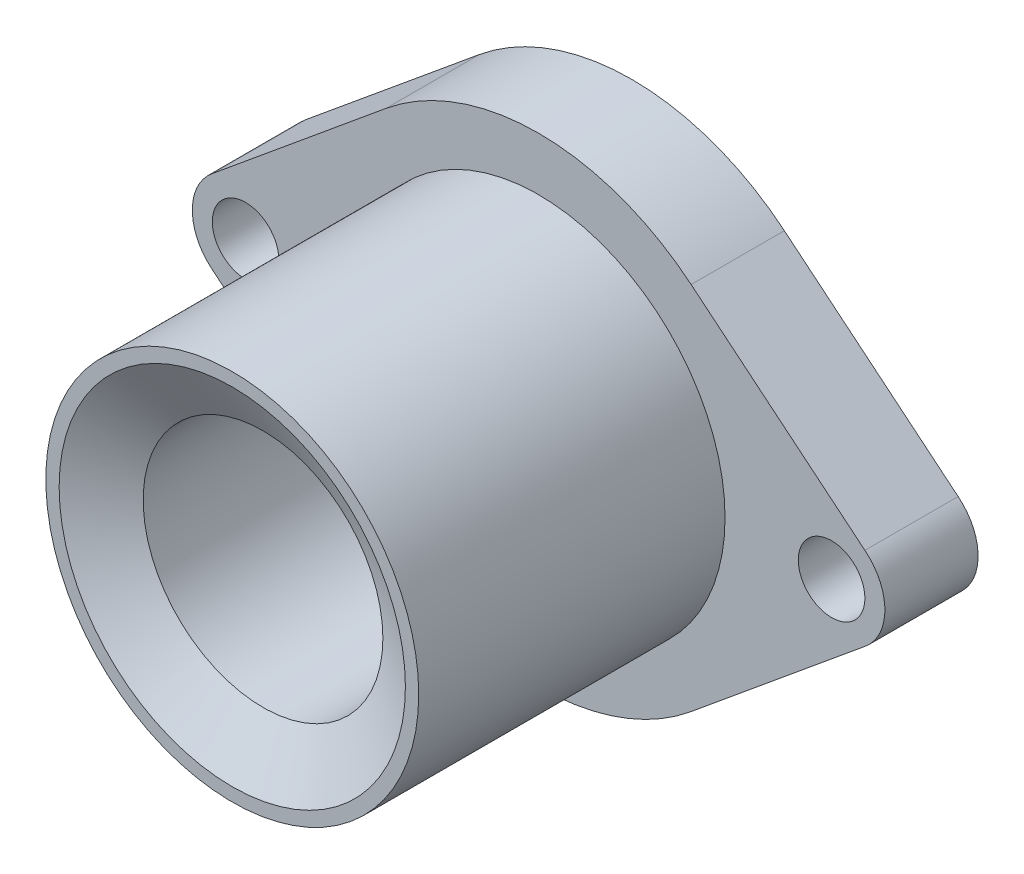
SolidWorks part; units mm, degrees
ref_plane "前视基准面" through (0, 0, 0) normal (0, 0, 1) x (1, 0, 0)
ref_plane "上视基准面" through (0, 0, 0) normal (0, 1, 0) x (1, 0, 0)
ref_plane "右视基准面" through (0, 0, 0) normal (1, 0, 0) x (0, 0, -1)
sketch "草图1" plane through (0, 0, 0) normal (0, 0, 1) x (1, 0, 0)
  line L0 (0, 0) -> (44.6917, 0) construction
  line L1 (0, 0) -> (0, 30.0219) construction
  line L2 (-24.5, 3.1225) -> (-11.4549, 13.8847)
  line L3 (24.5, 3.1225) -> (11.4549, 13.8847)
  line L4 (-24.5, -3.1225) -> (-11.4549, -13.8847)
  line L5 (24.5, -3.1225) -> (11.4549, -13.8847)
  arc A0 (-11.4549, -13.8847) -> (11.4549, -13.8847) centre (0, 0) ccw
  circle A2 centre (-22, 0) radius 2.5
  circle A3 centre (22, 0) radius 2.5
  arc A4 (-24.5, 3.1225) -> (-24.5, -3.1225) centre (-22, 0) ccw
  arc A5 (24.5, -3.1225) -> (24.5, 3.1225) centre (22, 0) ccw
  arc A6 (11.4549, 13.8847) -> (-11.4549, 13.8847) centre (0, 0) ccw
  circle A8 centre (0, 0) radius 14
  circle A9 centre (0, 0) radius 9
  dimension "D1" = 22
  dimension "D2" = 22
extrude "凸台-拉伸1" add sketch "草图1" along normal blind 7 contours L3 A6 L2 A4 L4 A0 L5 A5 A8 A2 A3 | A8 A9 | A9 region at (-17.575, 8.0157, 0) region at (-13.604, 0, 0) region at (0, 0, 0)
extrude "凸台-拉伸3" add sketch "草图1<5>" along normal blind 30 contours A8 A9 region at (-13.604, 0, 0)
sketch "草图1<5>" plane through (0, 0, 0) normal (0, 0, 1) x (1, 0, 0) same geometry as "草图1"
extrude "切除-拉伸2" cut sketch "草图1<6>" along normal blind 7 contours A9 region at (0, 0, 0)
sketch "草图1<6>" plane through (0, 0, 0) normal (0, 0, 1) x (1, 0, 0) same geometry as "草图1"
chamfer "倒角1" distance 4 angle 30 1 edges at (9, 0, 30) first distance on face at (9, 0, 30)
